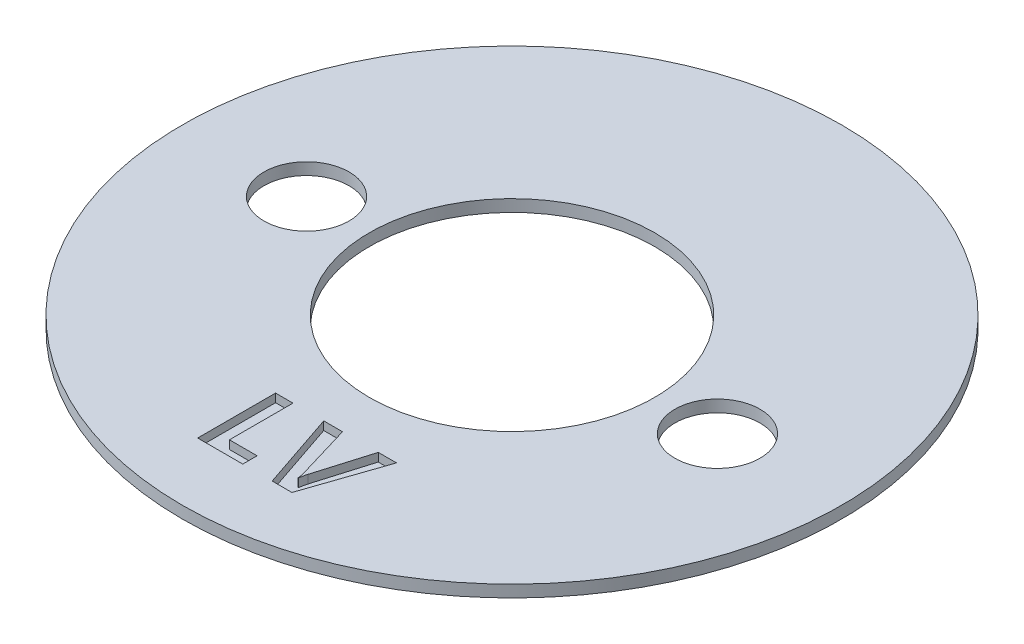
SolidWorks part; units mm, degrees
material "ABS"
ref_plane "Front Plane" through (0, 0, 0) normal (0, 0, 1) x (1, 0, 0)
ref_plane "Top Plane" through (0, 0, 0) normal (0, 1, 0) x (1, 0, 0)
ref_plane "Right Plane" through (0, 0, 0) normal (1, 0, 0) x (0, 0, -1)
sketch "Sketch1" plane through (0, 0, 0) normal (0, 1, 0) x (1, 0, 0)
  circle A0 centre (0, 0) radius 27.5
  dimension "D1" = 55
extrude "Boss-Extrude1" add sketch "Sketch1" along normal blind 1
sketch "Sketch4" plane through (0, 0, 0) normal (0, -1, 0) x (1, 0, 0)
  line L0 (-17.145, 0) -> (17.145, 0) construction
  circle A4 centre (-17.145, 0) radius 3.55
  circle A5 centre (0, 0) radius 11.9062
  circle A6 centre (17.145, 0) radius 3.55
  dimension "D1" = 34.29
  dimension "D2" = 23.8125
  dimension "D3" = 7.1
extrude "Cut-Extrude2" cut sketch "Sketch4" against normal through all
sketch "Sketch2" plane through (0, 1, 0) normal (0, 1, 0) x (1, 0, 0)
  line L0 (-5, -22) -> (5, -22) construction
  line L1 (0, 0) -> (0, -22) construction
  text T0 "LV" font "Nirmala UI" height 6.5
  dimension "D1" = 10
  dimension "D2" = 22
extrude "Cut-Extrude1" cut sketch "Sketch2" against normal offset from surface (0.7 mm away) 0.3 up to face at (-17.145, 0, -3.55)
